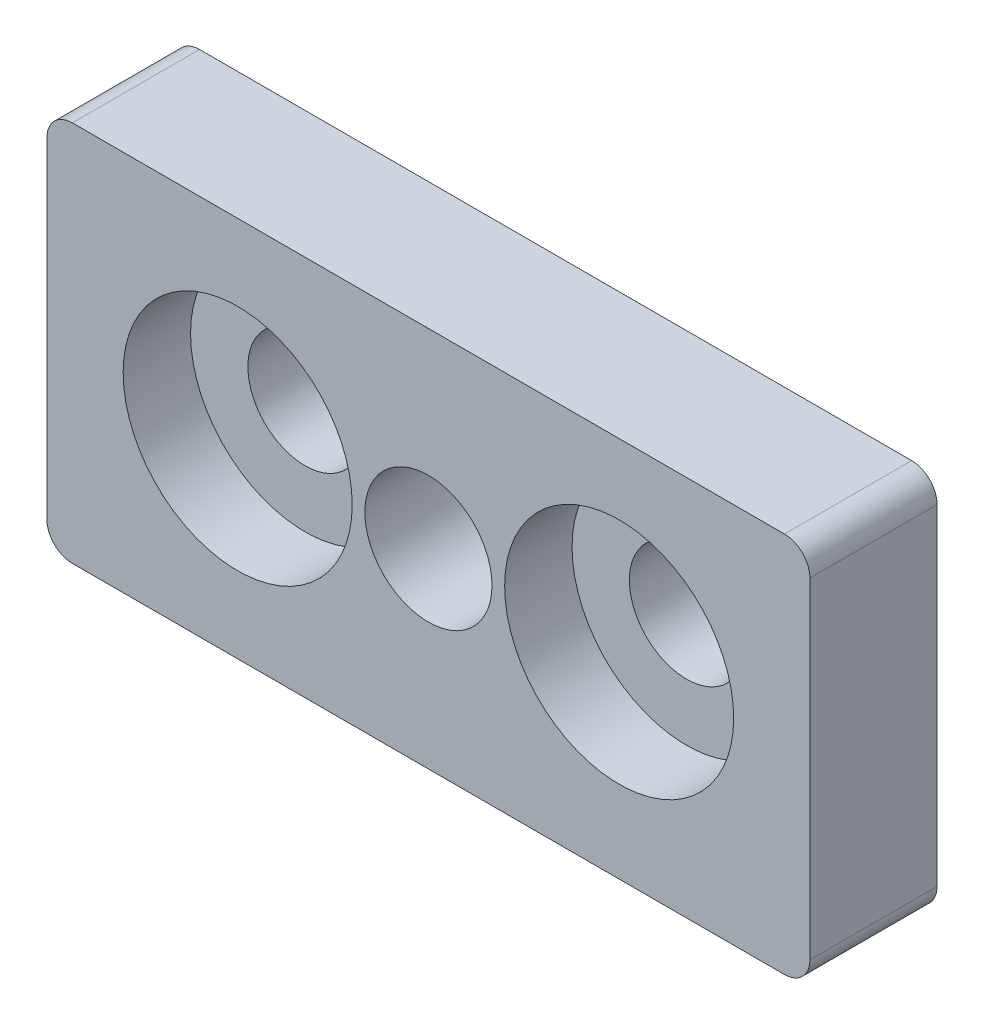
SolidWorks part; units mm, degrees
ref_plane "Front Plane" through (0, 0, 0) normal (0, 0, 1) x (1, 0, 0)
ref_plane "Top Plane" through (0, 0, 0) normal (0, 1, 0) x (1, 0, 0)
ref_plane "Right Plane" through (0, 0, 0) normal (1, 0, 0) x (0, 0, -1)
ref_plane "Plane1" through (0, 0, 10) normal (0, 0, 1) x (1, 0, 0)
sketch "Sketch1" plane through (0, 0, 10) normal (0, 0, 1) x (1, 0, 0)
  line L0 (30, 15) -> (-30, 15)
  line L1 (-30, 15) -> (-30, -15)
  line L2 (-30, -15) -> (30, -15)
  line L3 (30, -15) -> (30, 15)
extrude "Boss-Extrude1" add sketch "Sketch1" against normal blind 10
hole_wizard "Ø10.0 (10) Diameter Hole1" positions "Sketch3" profile "Sketch2" hole size "Ø10.0" standard "ANSI Metric"
sketch "Sketch3" plane through (0, 0, 10) normal (0, 0, 1) x (1, 0, 0)
  point P0 (0, 0)
sketch "Sketch2" plane through (0, 0, 10) normal (1, 0, 0) x (0, -1, 0)
  line L0 (0, 0) -> (0, 10)
  line L1 (0, 10) -> (5, 10)
  line L2 (5, 10) -> (5, 0)
  line L5 (5, 0) -> (0, 0)
  line L11 (0, -6.35) -> (0, 107.95) construction
  dimension "Thru Hole Dia." = 10
  dimension "Thru Hole Depth" = 10
hole_wizard "CBORE for M8 Hex Head Bolt1" positions "Sketch5" profile "Sketch4" counterbore size "M8" standard "ANSI Metric"
sketch "Sketch5" plane through (0, 0, 10) normal (0, 0, 1) x (1, 0, 0)
  point P0 (-15, 0)
  point P1 (15, 0.4628)
sketch "Sketch4" plane through (-15, 0, 10) normal (1, 0, 0) x (0, -1, 0)
  line L0 (0, 0) -> (0, 10)
  line L1 (0, 10) -> (4.5, 10)
  line L3 (4.5, 10) -> (4.5, 5.3)
  line L4 (4.5, 5.3) -> (9.0055, 5.3)
  line L5 (9.0055, 5.3) -> (9.0055, 0)
  line L7 (9.0055, 0) -> (0, 0)
  line L11 (0, -6.35) -> (0, 107.95) construction
  dimension "Thru Hole Dia." = 9
  dimension "Thru Hole Depth" = 10
  dimension "C'Bore Dia." = 18.011
  dimension "C'Bore Depth" = 5.3
fillet "Fillet1" radius 2 4 edges at (-30, -15, 5) (-30, 15, 5) (30, -15, 5) (30, 15, 5) tangent propagation no
